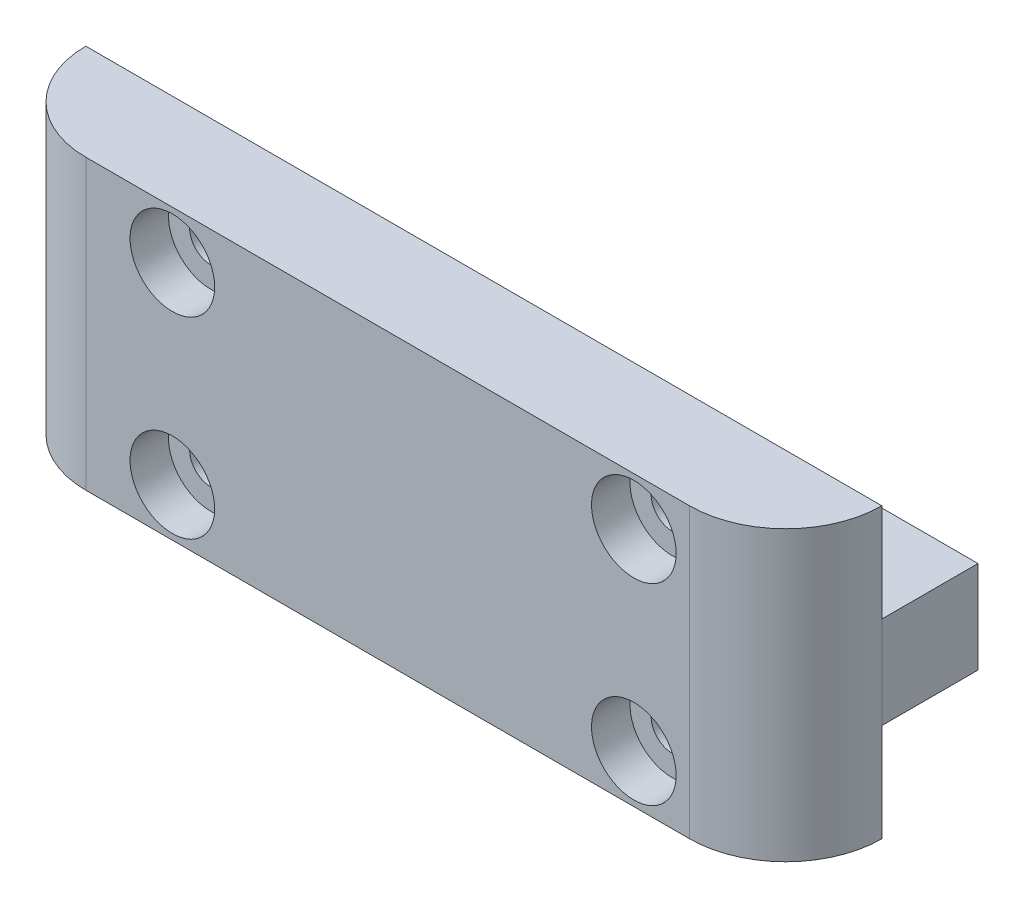
SolidWorks part; units mm, degrees
ref_plane "Front Plane" through (0, 0, 0) normal (0, 0, 1) x (1, 0, 0)
ref_plane "Top Plane" through (0, 0, 0) normal (0, 1, 0) x (1, 0, 0)
ref_plane "Right Plane" through (0, 0, 0) normal (1, 0, 0) x (0, 0, -1)
sketch "Sketch1" plane through (0, 0, 0) normal (0, 0, 1) x (1, 0, 0)
  line L0 (-20.7, 5) -> (20.7, 5) construction
  line L1 (-20.7, 7.5) -> (20.7, 7.5)
  line L2 (-20.7, 7.5) -> (-20.7, -7.5)
  line L3 (-20.7, -7.5) -> (20.7, -7.5)
  line L4 (20.7, 7.5) -> (20.7, -7.5)
  line L5 (-20.7, 7.5) -> (20.7, -7.5) construction
  line L6 (-20.7, -7.5) -> (20.7, 7.5) construction
  line L7 (-20.7, 0) -> (20.7, 0) construction
  circle A0 centre (-11.2, 5) radius 1.1
  circle A1 centre (-3.2, 5) radius 1.1 construction
  circle A2 centre (4.8, 5) radius 1.1 construction
  circle A3 centre (12.8, 5) radius 1.1
  circle A4 centre (12.8, -5) radius 1.1
  circle A5 centre (4.8, -5) radius 1.1 construction
  circle A6 centre (-3.2, -5) radius 1.1 construction
  circle A7 centre (-11.2, -5) radius 1.1
  point P0 (0, 0)
  dimension "D4" = 2.2
  dimension "D1" = 15
  dimension "D2" = 41.4
  dimension "D3" = 10
  dimension "D5" = 9.5
  dimension "D7" = 8
  dimension "D6" = 4
extrude "Boss-Extrude1" add sketch "Sketch1" along normal blind 5
sketch "Sketch2" plane through (0, 0, 0) normal (0, 0, 1) x (1, 0, 0)
  line L0 (20.7, -7.5) -> (20.7, 7.5) construction
  line L1 (-20.7, 2.4) -> (20.7, 2.4)
  line L2 (-20.7, 2.4) -> (-20.7, -2.4)
  line L3 (-20.7, -2.4) -> (20.7, -2.4)
  line L4 (20.7, 2.4) -> (20.7, -2.4)
  line L5 (-20.7, 2.4) -> (20.7, -2.4) construction
  line L6 (-20.7, -2.4) -> (20.7, 2.4) construction
  point P0 (0, 0)
  dimension "D1" = 4.8
extrude "Boss-Extrude2" add sketch "Sketch2" against normal blind 5
hole_wizard "CBORE for M2 SHCS1" positions "Sketch4" profile "Sketch3" counterbore size "M2" standard "Ansi Metric" end condition through all
sketch "Sketch4" plane through (0, 0, 5) normal (0, 0, 1) x (1, 0, 0)
  point P0 (-11.2, 5)
  point P1 (12.8, 5)
  point P4 (12.8, -5)
  point P7 (-11.2, -5)
sketch "Sketch3" plane through (-11.2, 5, 5) normal (1, 0, 0) x (0, -1, 0)
  line L0 (0, 0) -> (0, 10)
  line L1 (0, 10) -> (1.1, 10)
  line L3 (1.1, 10) -> (1.1, 2)
  line L4 (1.1, 2) -> (2.2, 2)
  line L5 (2.2, 2) -> (2.2, 0)
  line L7 (2.2, 0) -> (0, 0)
  line L11 (0, -6.35) -> (0, 107.95) construction
  dimension "Thru Hole Dia." = 2.2
  dimension "Thru Hole Depth" = 10
  dimension "C'Bore Dia." = 4.4
  dimension "C'Bore Depth" = 2
fillet "Fillet1" radius 5 2 edges at (-20.7, 0, 5) (20.7, 0, 5)
